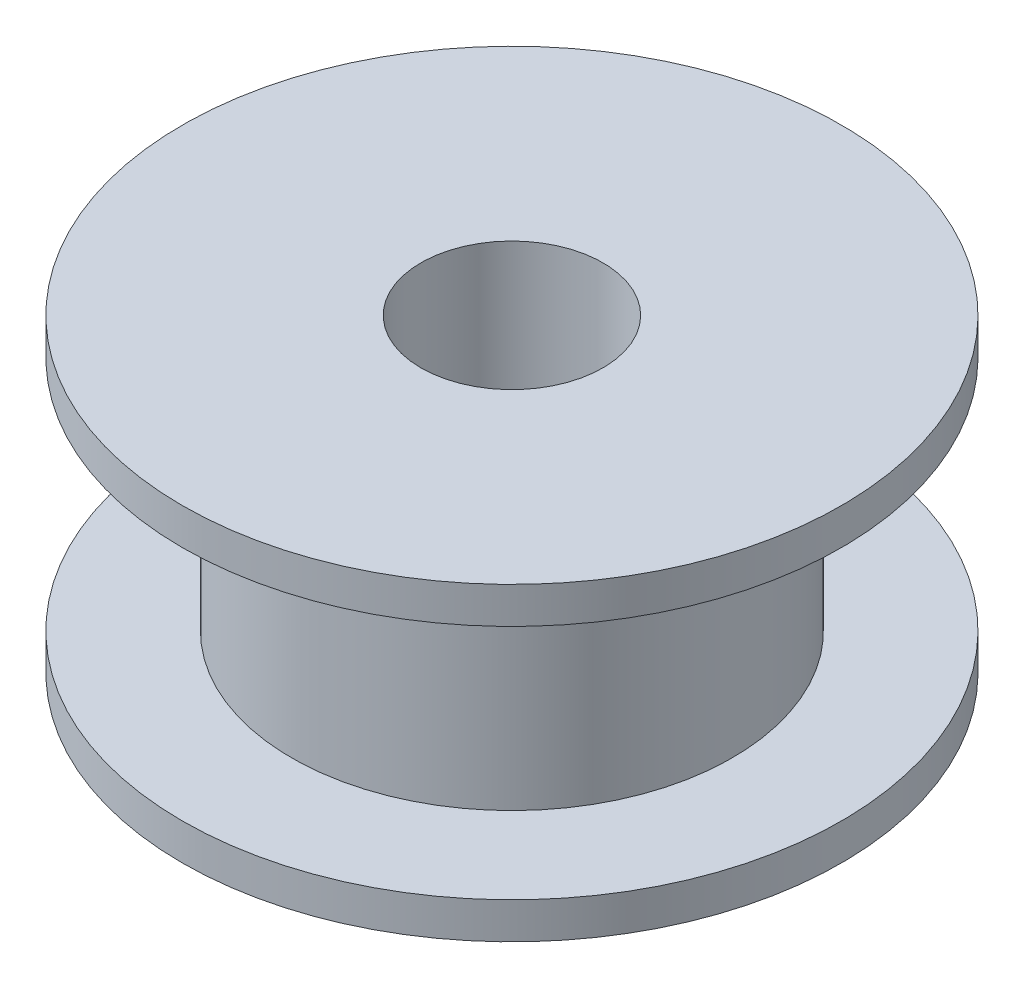
SolidWorks part; units mm, degrees
ref_plane "Front Plane" through (0, 0, 0) normal (0, 0, 1) x (1, 0, 0)
ref_plane "Top Plane" through (0, 0, 0) normal (0, 1, 0) x (1, 0, 0)
ref_plane "Right Plane" through (0, 0, 0) normal (1, 0, 0) x (0, 0, -1)
sketch "Sketch1" plane through (0, 0, 0) normal (0, 1, 0) x (1, 0, 0)
  circle A0 centre (0, 0) radius 9.05
  circle A1 centre (0, 0) radius 6.05
  circle A2 centre (0, 0) radius 2.5
  dimension "D1" = 18.1
  dimension "D2" = 12.1
  dimension "D3" = 5
extrude "Boss-Extrude1" add sketch "Sketch1" along normal blind 1 contours A0 A1 | A1 A2 region at (-8.794, 0, 0) region at (-5.8789, 0, 0)
extrude "Boss-Extrude2" add sketch "Sketch1<3>" along normal blind 3.25 from surface contours A1 A2 region at (-5.8789, 0, 0) starting at face at (0, 1, 9.05)
sketch "Sketch1<3>" plane through (0, 0, 0) normal (0, 1, 0) x (1, 0, 0) same geometry as "Sketch1"
mirror "Mirror2" about plane through (0, 4.25, 0) normal (0, 1, 0) of bodies 102
